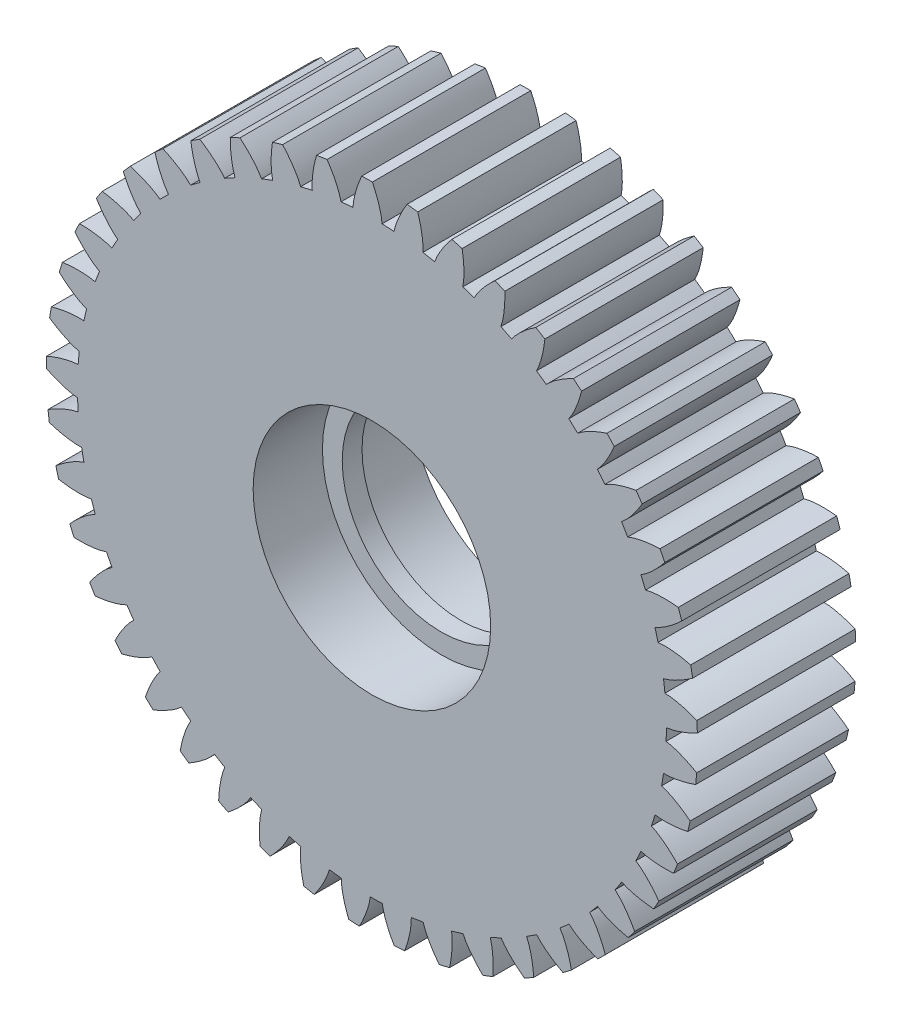
SolidWorks part; units mm, degrees
material "ABS"
ref_plane "Front Plane" through (0, 0, 0) normal (0, 0, 1) x (1, 0, 0)
ref_plane "Top Plane" through (0, 0, 0) normal (0, 1, 0) x (1, 0, 0)
ref_plane "Right Plane" through (0, 0, 0) normal (1, 0, 0) x (0, 0, -1)
sketch "Sketch1" plane through (0, 0, 0) normal (0, 0, 1) x (1, 0, 0)
  circle A0 centre (0, 0) radius 16.45
  dimension "D1" = 32.9
extrude "Boss-Extrude1" add sketch "Sketch1" along normal mid plane 8
sketch "Sketch2" plane through (0, 0, 0) normal (0, 0, 1) x (1, 0, 0)
  line L0 (0, 0) -> (14.8002, 0) construction
  line L1 (0, 0) -> (15.7468, -0.315) construction
  line L2 (0, 0) -> (14.7883, -0.5919) construction
  line L3 (14.8002, 0) -> (14.875, 0)
  line L4 (14.7883, -0.5919) -> (14.8631, -0.5949)
  circle A0 centre (0, 0) radius 15.75 construction
  circle A1 centre (0, 0) radius 14.8002 construction
  circle A2 centre (0, 0) radius 14.875
  circle A3 centre (0, 0) radius 16.45 construction
  circle A4 centre (0, 0) radius 16.45
  spline S0 degree 4 poles (14.8002, 0) (14.8052, 0.0001) (14.8194, 0.0005) (14.8462, 0.0022) (14.8899, 0.0062) (14.9454, 0.0132) (15.017, 0.0244) (15.1012, 0.0403) (15.1933, 0.0606) (15.2931, 0.0858) (15.3922, 0.1137) (15.4907, 0.1439) (15.5885, 0.1763) (15.7063, 0.2183) (15.8469, 0.2722) (16.01, 0.3406) (16.1935, 0.4245) (16.3787, 0.5166) (16.5595, 0.6127) (16.7402, 0.716) (16.9138, 0.8203) (17.0919, 0.9349) (17.2553, 1.044) (17.4359, 1.1729) (17.5809, 1.279) (17.7694, 1.4262) (17.8798, 1.5153) (18.0081, 1.622) (18.0645, 1.6706) (18.0993, 1.7006) knots 0 0 0 0 0 0.005377 0.015084 0.028532 0.04661 0.064855 0.092111 0.119476 0.146842 0.174209 0.201575 0.228941 0.256307 0.307035 0.361767 0.4165 0.471232 0.525964 0.580697 0.635429 0.690161 0.744894 0.799626 0.854358 0.909091 0.954545 1 1 1 1 1 construction
  spline S1 degree 4 poles (14.8002, 0) (14.8052, 0.0001) (14.8194, 0.0005) (14.8462, 0.0022) (14.8899, 0.0062) (14.9454, 0.0132) (15.017, 0.0244) (15.1012, 0.0403) (15.1933, 0.0606) (15.2931, 0.0858) (15.3922, 0.1137) (15.4907, 0.1439) (15.5885, 0.1763) (15.7063, 0.2183) (15.8469, 0.2722) (16.01, 0.3406) (16.1935, 0.4245) (16.3787, 0.5166) (16.5595, 0.6127) (16.7402, 0.716) (16.9138, 0.8203) (17.0919, 0.9349) (17.2553, 1.044) (17.4359, 1.1729) (17.5809, 1.279) (17.7285, 1.3943) (17.8, 1.4512) (17.8364, 1.4807) knots 0 0 0 0 0 0.005377 0.015084 0.028532 0.04661 0.064855 0.092111 0.119476 0.146842 0.174209 0.201575 0.228941 0.256307 0.307035 0.361767 0.4165 0.471232 0.525964 0.580697 0.635429 0.690161 0.744894 0.799626 0.854358 0.909091 0.909091 0.909091 0.909091 0.909091
  spline S2 degree 4 poles (14.7883, -0.5919) (14.7934, -0.5922) (14.8075, -0.5932) (14.8342, -0.596) (14.8777, -0.6017) (14.9329, -0.611) (15.0041, -0.625) (15.0875, -0.6442) (15.1787, -0.6682) (15.2774, -0.6974) (15.3754, -0.7292) (15.4726, -0.7633) (15.5689, -0.7996) (15.685, -0.8462) (15.8233, -0.9058) (15.9836, -0.9806) (16.1636, -1.0718) (16.345, -1.1712) (16.5217, -1.2745) (16.6982, -1.3849) (16.8674, -1.4961) (17.0409, -1.6178) (17.1998, -1.7332) (17.3751, -1.8693) (17.5157, -1.9811) (17.6981, -2.1357) (17.8049, -2.2291) (17.9288, -2.3409) (17.9833, -2.3918) (18.0168, -2.4231) knots 0 0 0 0 0 0.005377 0.015084 0.028532 0.04661 0.064855 0.092111 0.119476 0.146842 0.174209 0.201575 0.228941 0.256307 0.307035 0.361767 0.4165 0.471232 0.525964 0.580697 0.635429 0.690161 0.744894 0.799626 0.854358 0.909091 0.954545 1 1 1 1 1 construction
  spline S3 degree 4 poles (14.7883, -0.5919) (14.7934, -0.5922) (14.8075, -0.5932) (14.8342, -0.596) (14.8777, -0.6017) (14.9329, -0.611) (15.0041, -0.625) (15.0875, -0.6442) (15.1787, -0.6682) (15.2774, -0.6974) (15.3754, -0.7292) (15.4726, -0.7633) (15.5689, -0.7996) (15.685, -0.8462) (15.8233, -0.9058) (15.9836, -0.9806) (16.1636, -1.0718) (16.345, -1.1712) (16.5217, -1.2745) (16.6982, -1.3849) (16.8674, -1.4961) (17.0409, -1.6178) (17.1998, -1.7332) (17.3751, -1.8693) (17.5157, -1.9811) (17.6586, -2.1022) (17.7278, -2.1619) (17.763, -2.1928) knots 0 0 0 0 0 0.005377 0.015084 0.028532 0.04661 0.064855 0.092111 0.119476 0.146842 0.174209 0.201575 0.228941 0.256307 0.307035 0.361767 0.4165 0.471232 0.525964 0.580697 0.635429 0.690161 0.744894 0.799626 0.854358 0.909091 0.909091 0.909091 0.909091 0.909091
  dimension "D1" = 31.5
  dimension "D2" = 29.6003
  dimension "D3" = 29.75
  dimension "D4" = 1.146
  dimension "D5" = 1.146
extrude "Cut-Extrude1" cut sketch "Sketch2" against normal through all both and the other way through all contours A2 S3 A4 S1 region at (15.7978, -0.316, 0)
pattern_circular "CirPattern2" count 45 over 360 about axis through (0, 0, 4) along (0, 0, -1) of "Cut-Extrude1"
sketch "Sketch3" plane through (0, 0, 4) normal (0, 0, 1) x (1, 0, 0)
  circle A0 centre (0, 0) radius 6
  dimension "D1" = 12
extrude "Cut-Extrude2" cut sketch "Sketch3" against normal blind 3.5
sketch "Sketch4" plane through (0, 0, 0.5) normal (0, 0, 1) x (1, 0, 0)
  circle A0 centre (0, 0) radius 5
  dimension "D1" = 10
extrude "Cut-Extrude3" cut sketch "Sketch4" against normal through all
mirror "Mirror1" about plane through (0, 0, 0) normal (0, 0, 1) of "Cut-Extrude2"
equation "\"Np\"= 45"
equation "\"module\"= 0.7"
equation "\"pressure angle\"= 20.0deg"
equation "\"h_a\"= 0.7"
equation "\"h_b\"= 0.875"
equation "\"clr_tip_root\"= 0.17500000000000004"
equation "\"dp_p\"= 31.499999999999996"
equation "\"db_p\"= 29.600317554756113"
equation "\"D1@Sketch1\"= \"dp_p\" + 2*\"h_a\" "
equation "\"fw_p\"= 8.0"
equation "\"D1@Boss-Extrude1\"=\"fw_p\""
equation "\"D1@Sketch2\"=\"dp_p\""
equation "\"D2@Sketch2\"= \"db_p\""
equation "\"D3@Sketch2\"=\"dp_p\"- 2*\"h_b\""
equation "\"alpha_p\"= 0.8539582918412343"
equation "\"D4@Sketch2\"= 360 / ( 4 * \"Np\" ) - \"alpha_p\""
equation "\"beta_p\"= 2.2920834163175314"
equation "\"D5@Sketch2\"= 360 / ( 4 * \"Np\" ) - \"alpha_p\""
equation "\"D1@CirPattern2\"=\"Np\""
equation "\"Nr\"= 108"
equation "\"pressure_angle\"= 20.0deg"
equation "\"h_f\"= 0.875"
equation "\"dp_r\"= 75.6"
equation "\"db_r\"= 71.04076213141467"
equation "\"fw_r\"= 8.0"
equation "\"alpha_r\"= 0.8539582918412449"
equation "\"beta_r\"= 3.374583250349157"
equation "\"bearing_ID\"= 55"
equation "\"bearing_OD\"= 72"
equation "\"bearing_height\"= 9"
equation "\"clearance_planet\"= 1.5"
equation "\"case_dist\"= 6.5"
equation "\"Motor_case_OD_max\"= 111.3"
equation "\"case_mounting_PCD\"= 103.8"
equation "\"bearing mount thickness\"= 8"
equation "\"case_mounting_hole_dia\"= 3"
equation "\"output_mounting_PCD\"= 80"
equation "\"output_mounting_hole_dia\"= 4"
equation "\"clearance_case_mount_holes_shell_thickness\"= 1"
equation "\"motor_case_OD_base\"= 101.8"
equation "\"sec_carrier_thickness\"= 5"
equation "\"sun_coupler_hub_thickness\"= 4"
equation "\"clearance_sun_coupler_sec_carrier\"= 1.5"
equation "\"clearance_motor_and_case\"= 5"
equation "\"motor_OD\"= 86.8"
equation "\"Motor_case_thickness\"= 2.5"
equation "\"Motor_case_ID\"= 96.8"
equation "\"case_mounting_hole_shift\"= 1.0"
equation "\"output_mounting_nut_wrench_size\"= 7"
equation "\"output_mounting_nut_thickness\"= 3.2"
equation "\"case_mounting_hole_allen_socket_dia\"= 5.5"
equation "\"output_mounting_nut_depth\"= 3"
equation "\"case_mounting_bolt_depth\"= 4.5"
equation "\"Ns\"= 18"
equation "\"ring_radial_thickness\"= 5.0"
equation "\"ring_OD\"= 85.6"
equation "\"ring_to_chamfer_clearance\"= 2"
equation "\"Motor_case_OD_base_to_chamfer\"= 5"
equation "\"pattern_offset_from_motor_case_OD_base\"= 3"
equation "\"pattern_bulge_dia\"= 3"
equation "\"pattern_num_bulge\"= 18"
equation "\"pattern_depth\"= 2"
equation "\"motor_height\"= 26.5"
equation "\"case_mounting_wrench_size\"= 5.5"
equation "\"case_mounting_nut_clearance\"= 2"
equation "\"base_plate_thickness\"= 4"
equation "\"case_mounting_nut_thickness\"= 2.4"
equation "\"case_mounting_surface_height\"= 4"
equation "\"motor_mount_hole_PCD\"= 32"
equation "\"motor_mount_hole_dia\"= 4"
equation "\"motor_mount_hole_num\"= 4"
equation "\"central_hole_offset_from_motor_mount_PCD\"= 5"
equation "\"wire_slot_dist_from_center\"= 30"
equation "\"wire_slot_length\"= 10"
equation "\"wire_slot_radius\"= 4"
equation "\"driver_upper_holes_dist_from_center\"= 23"
equation "\"driver_lower_holes_dist_from_center\"= 15"
equation "\"driver_side_holes_dist_from_center\"= 20"
equation "\"driver_mount_holes_dia\"= 2.5"
equation "\"driver_mount_inserts_OD\"= 3.5"
equation "\"driver_mount_thickness\"= 1.5"
equation "\"driver_mount_height\"= 4"
equation "\"air_flow_hole_offset\"= 3"
equation "\"num_planet\"= 3"
equation "\"planet_pin_bolt_dia\"= 5"
equation "\"planet_pin_socket_head_dia\"= 8.5"
equation "\"carrier_PCD\"= 44.099999999999994"
equation "\"planet_shaft_dia\"= 8"
equation "\"planet_shaft_step_offset\"= 1"
equation "\"carrier_trapezoidal_support_sun_offset\"= 5"
equation "\"carrier_trapezoidal_support_hole_PCD_offset_bearing_ID\"= 4"
equation "\"carrier_trapezoidal_support_hole_dia\"= 3"
equation "\"carrier_trapezoidal_support_hole_socket_head_dia\"= 5.5"
equation "\"carrier_bearing_step_width\"= 1.5"
equation "\"standard_clearance_1_5mm\"= 1.5"
equation "\"standard_fillet_1_5mm\"= 1.5"
equation "\"sun_shaft_bearing_OD\"= 16"
equation "\"sun_shaft_bearing_width\"= 5"
equation "\"standard_bearing_insertion_chamfer\"= 0.5"
equation "\"carrier_trapezoidal_support_hole_wrench_size\"= 5.5"
equation "\"planet_pin_bolt_wrench_size\"= 8"
equation "\"planet_bearing_OD\"= 12"
equation "\"planet_bearing_width\"= 3.5"
equation "\"planet_bore\"= 10"
equation "\"D1@Cut-Extrude2\"=\"planet_bearing_width\""
equation "\"D1@Sketch3\"=\"planet_bearing_OD\""
equation "\"D1@Sketch4\"=\"planet_bore\""
